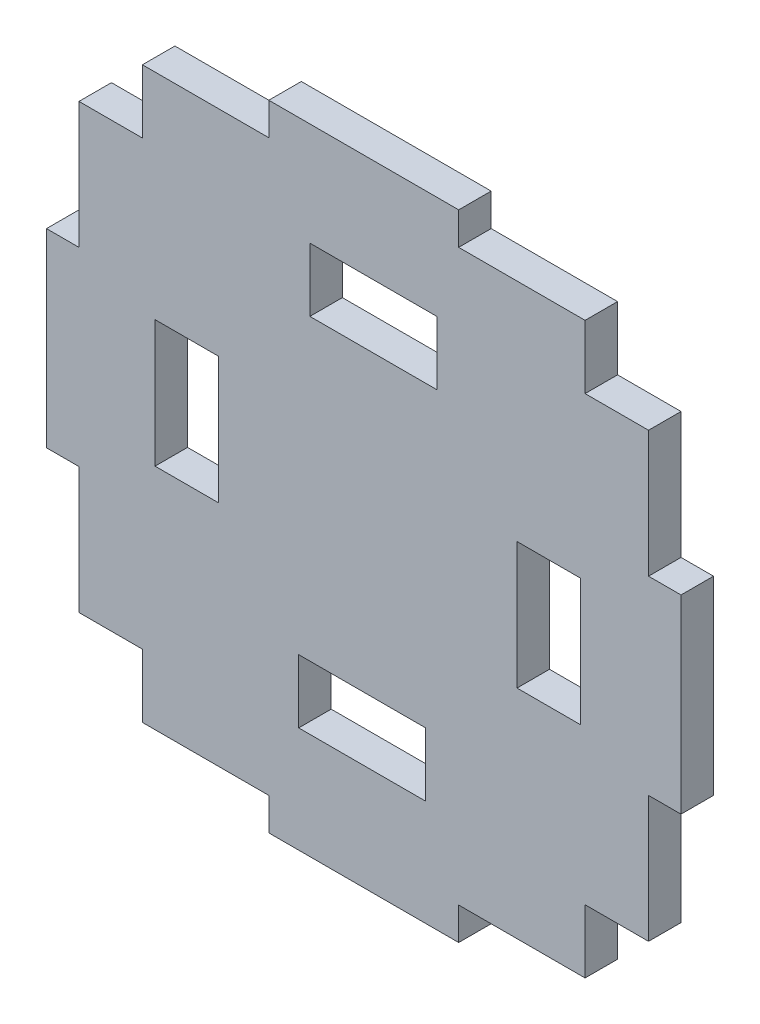
SolidWorks part; units mm, degrees
ref_plane "Front Plane" through (0, 0, 0) normal (0, 0, 1) x (1, 0, 0)
ref_plane "Top Plane" through (0, 0, 0) normal (0, 1, 0) x (1, 0, 0)
ref_plane "Right Plane" through (0, 0, 0) normal (1, 0, 0) x (0, 0, -1)
sketch "Sketch1" plane through (0, 0, 0) normal (0, 0, 1) x (1, 0, 0)
  line L0 (31.0404, 97.1976) -> (60.9604, 97.1976)
  line L1 (31.0404, -2.8024) -> (60.9604, -2.8024)
  line L3 (-3.9996, 32.2376) -> (-3.9996, 62.1576)
  line L4 (96.0004, 32.2376) -> (96.0004, 62.1576)
  line L7 (-3.9996, 62.1576) -> (1.1204, 62.1576)
  line L8 (1.1204, 92.0776) -> (1.1204, 62.1576)
  line L11 (-3.9996, 32.2376) -> (1.1204, 32.2376)
  line L12 (1.1204, 2.3176) -> (1.1204, 32.2376)
  line L15 (1.1204, 92.0776) -> (31.0404, 92.0776)
  line L16 (31.0404, 97.1976) -> (31.0404, 92.0776)
  line L19 (90.8804, 92.0776) -> (60.9604, 92.0776)
  line L20 (60.9604, 97.1976) -> (60.9604, 92.0776)
  line L22 (90.8804, 92.0776) -> (90.8804, 62.1576)
  line L23 (90.8804, 62.1576) -> (96.0004, 62.1576)
  line L25 (96.0004, 32.2376) -> (90.8804, 32.2376)
  line L27 (90.8804, 2.3176) -> (60.9604, 2.3176)
  line L28 (90.8804, 32.2376) -> (90.8804, 2.3176)
  line L31 (60.9604, 2.3176) -> (60.9604, -2.8024)
  line L33 (1.1204, 2.3176) -> (31.0404, 2.3176)
  line L36 (31.0404, 2.3176) -> (31.0404, -2.8024)
  dimension "D1" = 100
  dimension "D2" = 5.12
  dimension "D3" = 100
extrude "Boss-Extrude1" add sketch "Sketch1" along normal blind 5.12
sketch "Sketch2" plane through (0, 0, 5.12) normal (0, 0, 1) x (1, 0, 0)
  line L0 (23.108, 58.2888) -> (23.108, 38.2888)
  line L1 (1.1204, 92.0776) -> (11.1204, 92.0776)
  line L2 (1.1204, 92.0776) -> (1.1204, 82.0776)
  line L3 (1.1204, 82.0776) -> (11.1204, 82.0776)
  line L4 (11.1204, 92.0776) -> (11.1204, 82.0776)
  line L5 (90.8804, 92.0776) -> (80.8804, 92.0776)
  line L6 (90.8804, 92.0776) -> (90.8804, 82.0776)
  line L7 (90.8804, 82.0776) -> (80.8804, 82.0776)
  line L8 (80.8804, 92.0776) -> (80.8804, 82.0776)
  line L9 (90.8804, 2.3176) -> (80.8804, 2.3176)
  line L10 (90.8804, 2.3176) -> (90.8804, 12.3176)
  line L11 (90.8804, 12.3176) -> (80.8804, 12.3176)
  line L12 (80.8804, 2.3176) -> (80.8804, 12.3176)
  line L13 (1.1204, 2.3176) -> (11.1204, 2.3176)
  line L14 (1.1204, 2.3176) -> (1.1204, 12.3176)
  line L15 (1.1204, 12.3176) -> (11.1204, 12.3176)
  line L16 (11.1204, 2.3176) -> (11.1204, 12.3176)
  line L17 (35.7493, 13.8852) -> (55.7493, 13.8852)
  line L18 (35.7493, 13.8852) -> (35.7493, 23.8852)
  line L19 (35.7493, 23.8852) -> (55.7493, 23.8852)
  line L20 (55.7493, 13.8852) -> (55.7493, 23.8852)
  line L21 (13.108, 38.2888) -> (23.108, 38.2888)
  line L22 (13.108, 58.2888) -> (13.108, 38.2888)
  line L23 (13.108, 58.2888) -> (23.108, 58.2888)
  line L24 (57.5115, 70.9301) -> (37.5115, 70.9301)
  line L25 (37.5115, 80.9301) -> (37.5115, 70.9301)
  line L26 (57.5115, 80.9301) -> (37.5115, 80.9301)
  line L27 (57.5115, 80.9301) -> (57.5115, 70.9301)
  line L28 (70.1528, 36.5265) -> (70.1528, 56.5265)
  line L29 (80.1528, 56.5265) -> (70.1528, 56.5265)
  line L30 (80.1528, 36.5265) -> (80.1528, 56.5265)
  line L31 (80.1528, 36.5265) -> (70.1528, 36.5265)
  point P20 (46.6304, 47.4076)
  dimension "D1" = 10
  dimension "D2" = 10
  dimension "D3" = 20
  dimension "D4" = 4
extrude "Cut-Extrude1" cut sketch "Sketch2" against normal through all
equation "\"mdf\"=\"mdf@fmv1.assembly\""
equation "\"D2@Sketch1\"=\"mdf\""
equation "\"D1@Boss-Extrude1\"=\"mdf\""
